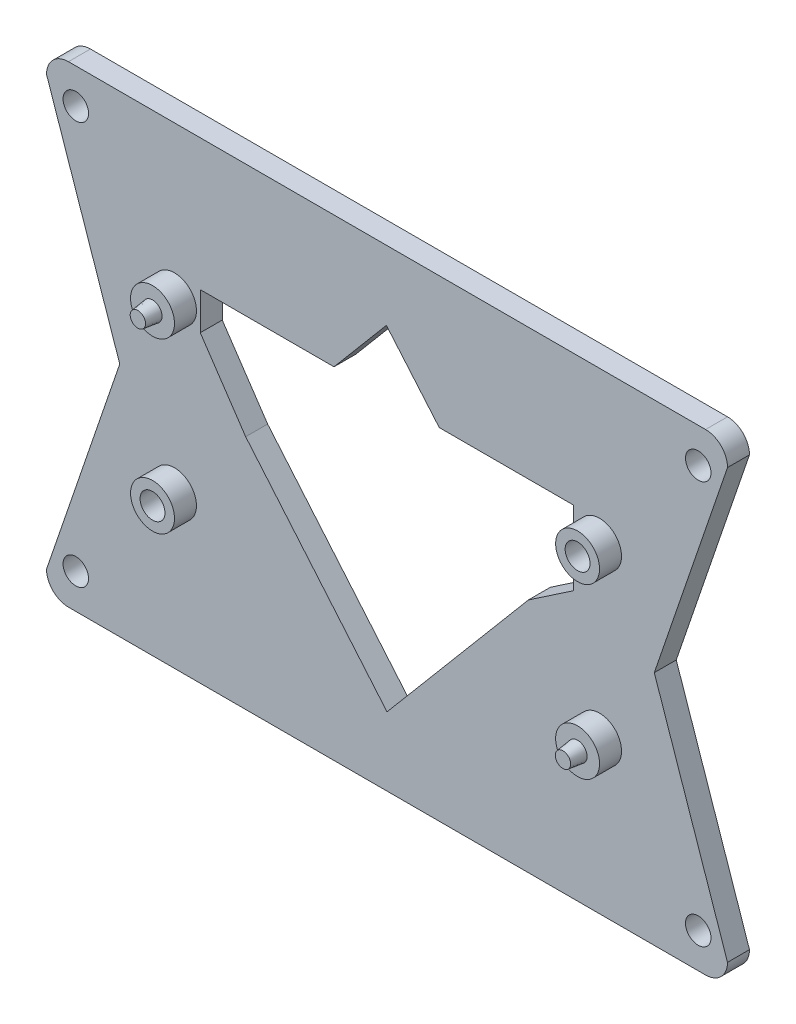
SolidWorks part; units mm, degrees
material "Custom Plastic"
ref_plane "Front Plane" through (0, 0, 0) normal (0, 0, 1) x (1, 0, 0)
ref_plane "Top Plane" through (0, 0, 0) normal (0, 1, 0) x (1, 0, 0)
ref_plane "Right Plane" through (0, 0, 0) normal (1, 0, 0) x (0, 0, -1)
sketch "Sketch2" plane through (0, 0, 0) normal (0, 0, 1) x (1, 0, 0)
  line L0 (46.5, 64.5181) -> (46.5, 0) construction
  line L1 (0, 0) -> (93, 0)
  line L2 (0, 0) -> (0, 64.5181)
  line L3 (0, 64.5181) -> (93, 64.5181)
  line L4 (93, 0) -> (93, 64.5181)
  line L5 (0, 64.5181) -> (5.6325, 64.5181)
  line L6 (0, 64.5181) -> (0, 59.1416)
  line L9 (0, 64.5181) -> (4, 59.759) construction
  line L10 (0, 59.1416) -> (5.6325, 64.5181) construction
  line L11 (0, 32.259) -> (93, 32.259) construction
  circle A0 centre (4, 59.759) radius 1.741
  circle A1 centre (89, 59.759) radius 1.741
  circle A2 centre (4, 4.759) radius 1.741
  circle A3 centre (89, 4.759) radius 1.741
  point P8 (2.5073, 61.5349)
  dimension "D1" = 85
  dimension "D2" = 55
extrude "Boss-Extrude1" add sketch "Sketch2" along normal blind 3 contours L1 L4 L3 L2 A3 A1 A0 A2 region at (46.5, 32.259, 0)
fillet "Fillet1" radius 3 4 edges at (0, 64.5181, 1.5) (93, 64.5181, 1.5) (93, 0, 1.5) (0, 0, 1.5)
sketch "Sketch3" plane through (0, 0, 3) normal (0, 0, 1) x (1, 0, 0)
  circle A0 centre (17.475, 20.734) radius 1.325 construction
  circle A1 centre (75.525, 43.784) radius 1.325 construction
  circle A2 centre (75.525, 20.734) radius 1.325 construction
  circle A3 centre (17.475, 43.784) radius 1.325 construction
  circle A4 centre (17.475, 20.734) radius 1.325
  circle A5 centre (75.525, 43.784) radius 1.325
  circle A6 centre (75.525, 20.734) radius 1.325
  circle A7 centre (17.475, 43.784) radius 1.325
  circle A8 centre (17.475, 43.784) radius 3
  circle A9 centre (17.475, 20.734) radius 3
  circle A10 centre (75.525, 20.734) radius 3
  circle A11 centre (75.525, 43.784) radius 3
extrude "Boss-Extrude2" add sketch "Sketch3" along normal blind 3 contours A8 A7 | A9 A4 | A4 | A11 A5 | A5 | A10 A6 | A6 | A7 | A8 | A7 region at (17.475, 20.734, 3) region at (75.525, 43.784, 3) region at (75.525, 20.734, 3) region at (17.475, 43.784, 3) region at (14.5599, 43.784, 3) region at (14.5599, 20.734, 3) region at (72.6099, 20.734, 3) region at (72.6099, 43.784, 3)
sketch "Sketch4" plane through (0, 0, 6) normal (0, 0, 1) x (1, 0, 0)
  circle A7 centre (75.525, 20.734) radius 1.3
  circle A8 centre (17.475, 43.784) radius 1.3
extrude "Boss-Extrude3" add sketch "Sketch4" along normal blind 2
sketch "Sketch5" plane through (0, 0, 6) normal (0, 0, 1) x (1, 0, 0)
  circle A0 centre (17.475, 20.734) radius 1.7
  circle A5 centre (75.525, 43.784) radius 1.7
extrude "Cut-Extrude1" cut sketch "Sketch5" against normal blind 11
chamfer "Chamfer1" distance 2 distance2 0.25 2 edges at (18.775, 43.784, 8) (76.825, 20.734, 8) first distance on face at (18.775, 43.784, 8) first distance on face at (76.825, 20.734, 8)
sketch "Sketch6" plane through (0, 0, 3) normal (0, 0, 1) x (1, 0, 0)
  line L0 (0.1762, 32.4785) -> (93, 32.4785) construction
  line L1 (4, 4.759) -> (17.475, 20.734) construction
  line L2 (4.1582, 59.5714) -> (32242.2458, -38159.6084) construction
  line L3 (75.525, 43.784) -> (89, 59.759) construction
  line L12 (75.525, 20.734) -> (89, 4.759) construction
  line L13 (46.4148, 55.043) -> (27.1964, 32.259)
  line L14 (27.1964, 32.259) -> (46.5, 9.3741)
  line L15 (46.5, 9.3741) -> (65.8036, 32.259)
  line L16 (65.8036, 32.259) -> (46.4148, 55.043)
  circle A0 centre (89, 59.759) radius 1.741 construction
  circle A1 centre (89, 59.759) radius 1.741
  circle A2 centre (89, 4.759) radius 1.741 construction
  circle A3 centre (89, 4.759) radius 1.741
  circle A12 centre (4, 59.759) radius 1.741 construction
  circle A13 centre (4, 59.759) radius 1.741
  circle A14 centre (4, 4.759) radius 1.741 construction
  circle A15 centre (4, 4.759) radius 1.741
  circle A16 centre (17.475, 20.734) radius 3 construction
  circle A17 centre (75.525, 20.734) radius 3 construction
  circle A18 centre (75.525, 43.784) radius 3 construction
  circle A19 centre (17.475, 43.784) radius 3 construction
  circle A20 centre (75.525, 20.734) radius 3
  circle A21 centre (75.525, 43.784) radius 3
  circle A22 centre (17.475, 43.784) radius 3
  circle A23 centre (17.475, 20.734) radius 3
extrude "Cut-Extrude2" cut sketch "Sketch6" against normal blind 11 contours L16 L13 L14 L15
sketch "Sketch7" plane through (0, 0, 3) normal (0, 0, 1) x (1, 0, 0)
  line L6 (21, 46.559) -> (21, 41.459)
  line L7 (21, 41.459) -> (66.9, 41.459)
  line L12 (66.9, 41.459) -> (66.9, 36.459)
  line L13 (66.9, 36.459) -> (72, 36.459)
  line L14 (72, 36.459) -> (72, 46.559)
  line L15 (72, 46.559) -> (21, 46.559)
  line L16 (21, 46.559) -> (21, 41.459)
  line L17 (21, 41.459) -> (66.9, 41.459)
  line L18 (66.9, 41.459) -> (66.9, 36.459)
  line L19 (66.9, 36.459) -> (72, 36.459)
  line L20 (72, 36.459) -> (72, 46.559)
  line L21 (72, 46.559) -> (21, 46.559)
  dimension "D1" = 0
extrude "Cut-Extrude3" cut sketch "Sketch7" against normal blind 11
sketch "Sketch8" plane through (0, 0, 0) normal (0, 0, -1) x (-1, 0, 0)
  line L0 (-72, 36.459) -> (-65.8036, 32.259)
  line L1 (-27.1964, 32.259) -> (-21, 41.459)
  line L2 (-72, 36.459) -> (-66.9, 41.459)
  line L3 (-66.9, 41.459) -> (-57.9745, 41.459)
  line L4 (-57.9745, 41.459) -> (-65.8036, 32.259)
  line L5 (-27.1964, 32.259) -> (-34.9567, 41.459)
  line L6 (-34.9567, 41.459) -> (-21, 41.459)
  circle A0 centre (-17.475, 20.734) radius 1.7 construction
  circle A1 centre (-75.525, 43.784) radius 1.7 construction
  circle A2 centre (-17.475, 20.734) radius 1.7
  circle A3 centre (-75.525, 43.784) radius 1.7
  circle A4 centre (-75.525, 43.784) radius 3
  circle A5 centre (-17.475, 20.734) radius 3
extrude "Cut-Extrude4" cut sketch "Sketch8" against normal blind 1.5
sketch "Sketch9" plane through (0, 0, 1.5) normal (0, 0, -1) x (-1, 0, 0)
  line L3 (-34.9567, 41.459) -> (-27.1964, 32.259)
  line L4 (-27.1964, 32.259) -> (-21, 41.459)
  line L5 (-66.9, 36.459) -> (-72, 36.459)
  line L6 (-72, 36.459) -> (-65.8036, 32.259)
  line L7 (-65.8036, 32.259) -> (-57.9745, 41.459)
  line L8 (-57.9745, 41.459) -> (-66.9, 41.459)
  line L9 (-66.9, 41.459) -> (-66.9, 36.459)
  line L10 (-66.9, 36.459) -> (-72, 36.459)
  line L11 (-72, 36.459) -> (-65.8036, 32.259)
  line L12 (-65.8036, 32.259) -> (-57.9745, 41.459)
  line L13 (-57.9745, 41.459) -> (-66.9, 41.459)
  line L14 (-66.9, 41.459) -> (-66.9, 36.459)
  line L15 (-21, 41.459) -> (-34.9567, 41.459)
  line L16 (-34.9567, 41.459) -> (-27.1964, 32.259)
  line L17 (-27.1964, 32.259) -> (-21, 41.459)
  line L18 (-21, 41.459) -> (-34.9567, 41.459)
  dimension "D1" = 0
  dimension "D2" = 0
extrude "Cut-Extrude5" cut sketch "Sketch9" against normal blind 1.5 contours L10 L11 L12 L13 L14 | L16 L17 L18
sketch "Sketch10" plane through (0, 0, 3) normal (0, 0, 1) x (1, 0, 0)
  line L0 (0, 32.259) -> (10, 32.259)
  line L1 (10, 32.259) -> (0, 3)
  line L2 (10, 32.259) -> (0, 61.5181)
  line L3 (93, 32.259) -> (83, 32.259)
  line L4 (90, 64.5181) -> (3, 64.5181)
  line L5 (0, 61.5181) -> (0, 3)
  line L6 (3, 0) -> (90, 0)
  line L7 (93, 3) -> (93, 61.5181)
  line L8 (90, 64.5181) -> (3, 64.5181)
  line L9 (0, 61.5181) -> (0, 3)
  line L10 (3, 0) -> (90, 0)
  line L11 (93, 3) -> (93, 61.5181)
  line L12 (83, 32.259) -> (93, 61.5181)
  line L13 (83, 32.259) -> (93, 3)
  arc A4 (3, 64.5181) -> (0, 61.5181) centre (3, 61.5181) ccw
  arc A5 (0, 3) -> (3, 0) centre (3, 3) ccw
  arc A6 (90, 0) -> (93, 3) centre (90, 3) ccw
  arc A7 (93, 61.5181) -> (90, 64.5181) centre (90, 61.5181) ccw
  arc A8 (3, 64.5181) -> (0, 61.5181) centre (3, 61.5181) ccw
  arc A9 (0, 3) -> (3, 0) centre (3, 3) ccw
  arc A10 (90, 0) -> (93, 3) centre (90, 3) ccw
  arc A11 (93, 61.5181) -> (90, 64.5181) centre (90, 61.5181) ccw
  line M28 (0, 61.5181) -> (0, 3)
  line M32 (93, 3) -> (93, 61.5181)
  dimension "D1" = 0
extrude "Cut-Extrude6" cut sketch "Sketch10" against normal blind 3 contours L0 L2 M28 | L1 L0 M28 | L12 L3 M32 | L3 L13 M32 region at (3.3333, 42.012, 3) region at (3.3333, 22.506, 3) region at (89.6667, 42.012, 3) region at (89.6667, 22.506, 3)
